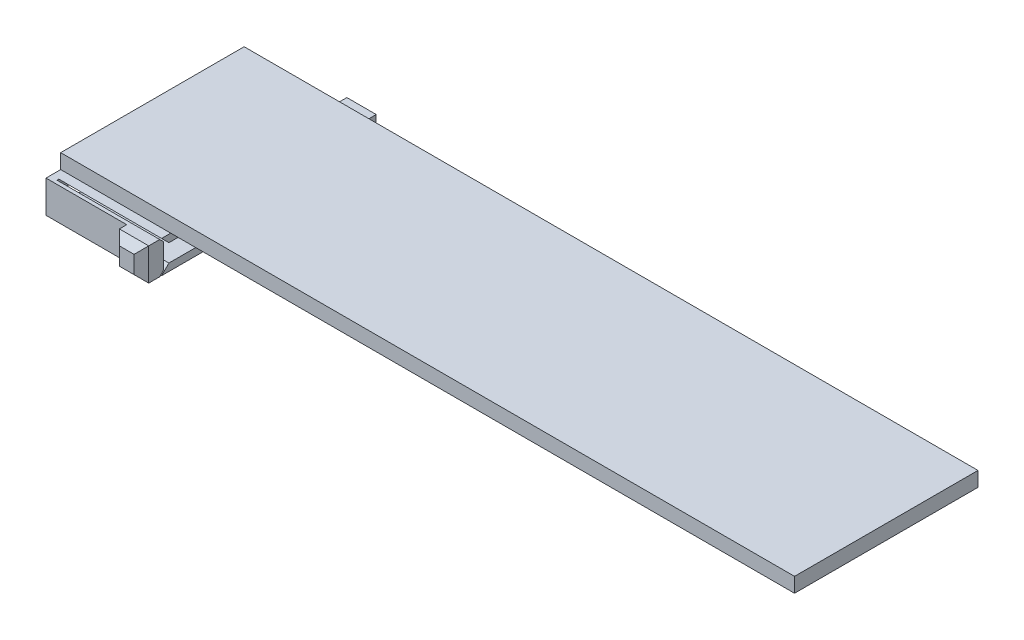
SolidWorks part; units mm, degrees
ref_plane "Front Plane" through (0, 0, 0) normal (0, 0, 1) x (1, 0, 0)
ref_plane "Top Plane" through (0, 0, 0) normal (0, 1, 0) x (1, 0, 0)
ref_plane "Right Plane" through (0, 0, 0) normal (1, 0, 0) x (0, 0, -1)
sketch "Sketch2" plane through (0, 0, 0) normal (0, 0, 1) x (1, 0, 0)
  line L0 (6.5593, 5.191) -> (9.5593, 3.691)
  line L1 (9.5593, 3.691) -> (9.5593, 5.191)
  line L2 (9.5593, 5.191) -> (9.5593, 6.191)
  line L3 (9.5593, 6.191) -> (-5.4407, 6.191)
  line L4 (-5.4407, 6.191) -> (-5.4407, 1.791)
  line L5 (-5.4407, 1.791) -> (9.5593, 1.791)
  line L6 (9.5593, 1.791) -> (9.5593, 2.791)
  line L7 (9.5593, 2.791) -> (-4.4407, 2.791)
  line L8 (-4.4407, 2.791) -> (-4.4407, 5.191)
  line L9 (-4.4407, 5.191) -> (6.5593, 5.191)
  point P2 (0, 0)
  dimension "D1" = 1.5
  dimension "D2" = 3
  dimension "D3" = 1
  dimension "D4" = 1
  dimension "D5" = 1
  dimension "D6" = 2.4
  dimension "D7" = 15
extrude "Boss-Extrude1" add sketch "Sketch2" against normal blind 29
sketch "Sketch3" plane through (9.5593, 0, 0) normal (1, 0, 0) x (0, 0, -1)
  line L0 (0, 3.691) -> (0, 6.191) construction
  line L1 (0, 5.191) -> (4.5, 5.191)
  line L2 (0, 5.191) -> (0, 3.691)
  line L3 (0, 3.691) -> (4.5, 3.691)
  line L4 (4.5, 5.191) -> (4.5, 3.691)
  line L5 (29, 3.691) -> (0, 3.691) construction
  line L6 (29, 3.691) -> (29, 6.191) construction
  line L7 (24.5, 3.691) -> (29, 3.691)
  line L8 (24.5, 3.691) -> (24.5, 5.191)
  line L9 (24.5, 5.191) -> (29, 5.191)
  line L10 (29, 3.691) -> (29, 5.191)
  line L11 (29, 5.191) -> (0, 5.191) construction
  point P14 (0, 0)
  dimension "D1" = 20
extrude "Cut-Extrude1" cut sketch "Sketch3" against normal up to next
sketch "Sketch4" plane through (-5.4407, 0, 0) normal (-1, 0, 0) x (0, 0, 1)
  line L0 (-14.5, 5.191) -> (-14.5, 6.191) construction
  line L1 (-27, 5.191) -> (-2, 5.191)
  line L2 (-27, 5.191) -> (-27, 2.791)
  line L3 (-27, 2.791) -> (-2, 2.791)
  line L4 (-2, 5.191) -> (-2, 2.791)
  line L5 (-29, 6.191) -> (0, 6.191) construction
  line L6 (-29, 5.191) -> (0, 5.191) construction
  line L7 (-29, 2.791) -> (0, 2.791) construction
  dimension "D1" = 25
extrude "Cut-Extrude2" cut sketch "Sketch4" against normal up to next
fillet "Fillet1" radius 1 4 edges at (-5.4407, 3.991, -2) (-5.4407, 2.791, -14.5) (-5.4407, 3.991, -27) (-5.4407, 5.191, -14.5)
chamfer "Chamfer1" distance 1.75 angle 45 4 edges at (2.5593, 2.791, -29) (2.5593, 5.191, -29) (2.5593, 5.191, 0) (2.5593, 2.791, 0)
sketch "Sketch5" plane through (-4.4407, 0, 0) normal (1, 0, 0) x (0, 0, -1)
  line L1 (0, 1.791) -> (0, 6.191) construction
  line L4 (0, 1.791) -> (0, 6.191)
  line L5 (14.5, 1.791) -> (14.5, 50001.791) construction
  line L6 (28.25, 1.791) -> (0.75, 1.791) construction
  line L11 (0, 6.191) -> (0.5, 6.191)
  line L12 (0.5, 6.191) -> (1, 5.691)
  line L13 (1, 5.691) -> (1, 2.291)
  line L14 (1, 2.291) -> (0.5, 1.791)
  line L15 (0.5, 1.791) -> (0, 1.791)
  line L17 (28, 2.291) -> (28.5, 1.791)
  line L18 (28, 5.691) -> (28, 2.291)
  line L19 (28.5, 6.191) -> (28, 5.691)
  line L20 (29, 6.191) -> (28.5, 6.191)
  line L21 (29, 1.791) -> (29, 6.191)
  line L22 (28.5, 1.791) -> (29, 1.791)
  point P1 (1.0972, 5.1274)
  point P4 (0, 3.991)
  point P7 (0, 3.991)
  point P13 (14.5, 1.791)
  point P20 (1.1536, 2.6244)
  point P21 (0.9638, 2.291)
  dimension "D1" = 4.4
  dimension "D2" = 0.5
  dimension "D3" = 45
  dimension "D4" = 1
extrude "Boss-Extrude2" add sketch "Sketch5" along normal up to surface (14 mm away) up to face at (9.5593, 5.066, -14.5)
sketch "Sketch6" plane through (9.5593, 0, 0) normal (1, 0, 0) x (0, 0, -1)
  line L0 (14.5, 1.791) -> (14.5, 50001.791) construction
  line L1 (0, 6.191) -> (-2, 6.191)
  line L2 (0, 6.191) -> (0, 1.791)
  line L3 (0, 1.791) -> (-2, 1.791)
  line L4 (-2, 6.191) -> (-2, 1.791)
  line L9 (28.25, 1.791) -> (0.75, 1.791) construction
  line L10 (29, 1.791) -> (31, 1.791)
  line L11 (31, 6.191) -> (31, 1.791)
  line L12 (29, 6.191) -> (31, 6.191)
  line L13 (29, 6.191) -> (29, 1.791)
  point P17 (14.5, 1.791)
  dimension "D1" = 2
extrude "Boss-Extrude3" add sketch "Sketch6" against normal blind 4
chamfer "Chamfer2" distance 1 angle 45 8 edges at (7.5593, 1.791, 2) (5.5593, 3.991, 2) (7.5593, 6.191, 2) (9.5593, 3.991, 2) (7.5593, 6.191, -31) (5.5593, 3.991, -31) (7.5593, 1.791, -31) (9.5593, 3.991, -31)
sketch "Sketch7" plane through (0, 6.191, 0) normal (0, 1, 0) x (1, 0, 0)
  line L1 (94.5593, 2) -> (-5.4407, 2)
  line L2 (94.5593, 2) -> (94.5593, 27)
  line L3 (94.5593, 27) -> (-5.4407, 27)
  line L4 (-5.4407, 2) -> (-5.4407, 27)
  line L5 (-5.4407, 28) -> (-5.4407, 1) construction
  point P4 (-17.1496, 1.2583)
  point P8 (47.4311, 3.0781)
  point P11 (-5.4407, 14.5)
  point P12 (-5.4407, 14.5)
  dimension "D1" = 25
  dimension "D2" = 100
extrude "Boss-Extrude4" add sketch "Sketch7" along normal blind 2
